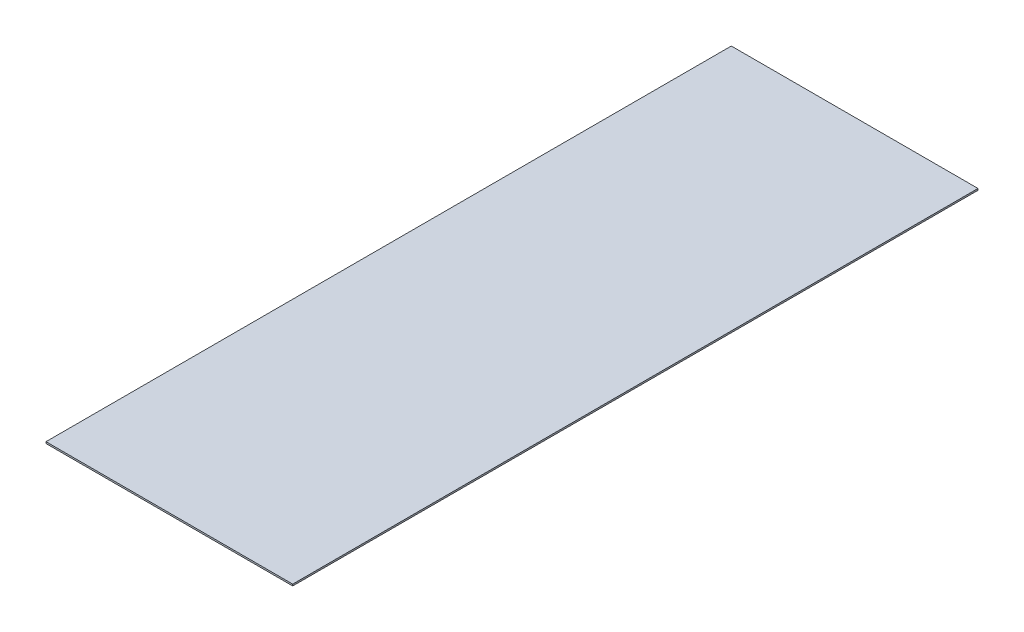
SolidWorks part; units mm, degrees
material "6061-T6 (SS)"
ref_plane "Front" through (0, 0, 0) normal (0, 0, 1) x (1, 0, 0)
ref_plane "Top" through (0, 0, 0) normal (0, 1, 0) x (1, 0, 0)
ref_plane "Right" through (0, 0, 0) normal (1, 0, 0) x (0, 0, -1)
sketch "Sketch1" plane through (0, 0, 0) normal (0, 1, 0) x (1, 0, 0)
  line L1 (0, 0) -> (114.3, 0)
  line L2 (0, 0) -> (0, 317.5)
  line L3 (0, 317.5) -> (114.3, 317.5)
  line L4 (114.3, 0) -> (114.3, 317.5)
  dimension "D1" = 317.5
  dimension "D2" = 114.3
sheet metal parameters "Sheet-Metal1" thickness 0.762 parameters "D1"=0.7366
base flange "Base-Flange1" sketch "Sketch1" thickness 0.762 reverse thickness direction no parameters "D1"=0.7366
flat pattern "Flat-Pattern1" [suppressed]
sketch "Bend-Lines1" plane through (0, 0, 0) normal (0, 1, 0) x (-1, 0, 0)
sketch3d "Bounding-Box1" [suppressed]
  line L0 (0, 317.5, 0) -> (0, 0, 0) construction
  line L1 (114.3, 317.5, 0) -> (114.3, 0, 0) construction
  line L2 (0, 317.5, 0) -> (114.3, 317.5, 0) construction
  line L3 (0, 0, 0) -> (114.3, 0, 0) construction
